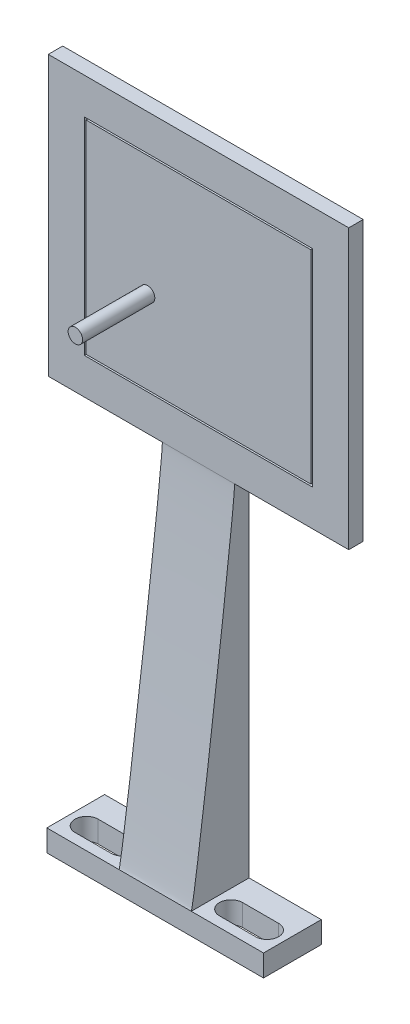
SolidWorks part; units mm, degrees
ref_plane "Front Plane" through (0, 0, 0) normal (0, 0, 1) x (1, 0, 0)
ref_plane "Top Plane" through (0, 0, 0) normal (0, 1, 0) x (1, 0, 0)
ref_plane "Right Plane" through (0, 0, 0) normal (1, 0, 0) x (0, 0, -1)
sketch "Sketch1" plane through (0, 0, 0) normal (0, 0, 1) x (1, 0, 0)
  line L0 (0, -16.6) -> (8.5, -16.6)
  line L1 (0, 0) -> (31.1, 0)
  line L2 (0, 0) -> (0, -28.1)
  line L3 (0, -28.1) -> (31.1, -28.1)
  line L4 (31.1, 0) -> (31.1, -28.1)
  circle A0 centre (8.5, -16.6) radius 1
  dimension "D5" = 2
  dimension "D1" = 28.1
  dimension "D2" = 31.1
  dimension "D3" = 11.5
  dimension "D4" = 8.5
extrude "Boss-Extrude2" add sketch "Sketch1" along normal blind 1.5 contours A0 L2 L3 L4 L1 | A0 region at (15.5754, -14.0408, 0)
sketch "Sketch3" plane through (0, 0, 1.5) normal (0, 0, 1) x (1, 0, 0)
  line L0 (0, -16.6) -> (8.5, -16.6) construction
  line L1 (0, -16.6) -> (8.5, -16.6)
  line L4 (31.1, 0) -> (0, 0)
  line L5 (0, 0) -> (0, -28.1)
  line L6 (0, -28.1) -> (31.1, -28.1)
  line L7 (31.1, -28.1) -> (31.1, 0)
  line L8 (31.1, 0) -> (0, 0)
  line L9 (0, 0) -> (0, -28.1)
  line L10 (0, -28.1) -> (31.1, -28.1)
  line L11 (31.1, -28.1) -> (31.1, 0)
  line L12 (31.1, 0) -> (0, 0)
  line L13 (31.1, -28.1) -> (31.1, 0)
  line L14 (0, -28.1) -> (31.1, -28.1)
  line L15 (0, 0) -> (0, -28.1)
  line L16 (31.1, 0) -> (0, 0)
  line L17 (31.1, -28.1) -> (31.1, 0)
  line L18 (0, -28.1) -> (31.1, -28.1)
  line L19 (0, 0) -> (0, -28.1)
  circle A1 centre (8.5, -16.6) radius 1
  circle A2 centre (8.5, -16.6) radius 1
  dimension "D1" = 0
  dimension "D2" = 0
  dimension "D3" = 0
extrude "Boss-Extrude3" add sketch "Sketch3" along normal blind 10 contours A2 region at (8.5, -15.6283, 1.5)
sketch "Sketch4" plane through (0, 0, 1.5) normal (0, 0, 1) x (1, 0, 0)
  line L1 (0, 0) -> (31.1, 0)
  line L2 (0, 0) -> (0, -28.1)
  line L3 (0, -28.1) -> (31.1, -28.1)
  line L4 (31.1, 0) -> (31.1, -28.1)
  line L5 (-0.25, 0.25) -> (31.35, 0.25)
  line L6 (-0.25, 0.25) -> (-0.25, -28.35)
  line L7 (-0.25, -28.35) -> (31.35, -28.35)
  line L8 (31.35, 0.25) -> (31.35, -28.35)
  line L9 (-5.25, 5.25) -> (36.35, 5.25)
  line L10 (-5.25, 5.25) -> (-5.25, -33.35)
  line L11 (-5.25, -33.35) -> (36.35, -33.35)
  line L12 (36.35, 5.25) -> (36.35, -33.35)
  dimension "D1" = 0.25
  dimension "D2" = 0.25
  dimension "D3" = 0.25
  dimension "D4" = 0.25
  dimension "D5" = 5
  dimension "D6" = 5
  dimension "D7" = 5
  dimension "D8" = 5
extrude "Boss-Extrude4" add sketch "Sketch4" against normal blind 2 separate body contours L12 L9 L10 L11 L5 L8 L7 L6 region at (15.55, 4.6825, 1.5)
sketch "Sketch6" plane through (0, -33.35, 0) normal (0, -1, 0) x (1, 0, 0)
  line L0 (0, 1.5) -> (31.1, 1.5) construction
  line L1 (10.55, 1.5) -> (20.55, 1.5)
  line L2 (10.55, 1.5) -> (10.55, -0.5)
  line L3 (10.55, -0.5) -> (20.55, -0.5)
  line L4 (20.55, 1.5) -> (20.55, -0.5)
  line L5 (-5.25, -0.5) -> (36.35, -0.5) construction
  line L6 (10.55, 1.5) -> (-5.25, 1.5) construction
  line L7 (20.55, 1.5) -> (36.35, 1.5) construction
  dimension "D1" = 10
extrude "Boss-Extrude5" add sketch "Sketch6" along normal blind 48.25
sketch "Sketch7" plane through (0, -81.6, 0) normal (0, -1, 0) x (1, 0, 0)
  line L0 (10.55, 1.5) -> (20.55, 1.5)
  line L1 (10.55, -0.5) -> (20.55, -0.5)
  line L5 (-5.25, 1.5) -> (10.55, 1.5) construction
  line L9 (0.55, 7.5) -> (0.55, 1.5)
  line L11 (30.55, 7.5) -> (30.55, 1.5)
  line L12 (20.55, 1.5) -> (36.35, 1.5) construction
  line L13 (30.55, 1.5) -> (20.55, 1.5)
  line L16 (0.55, 1.5) -> (10.55, 1.5)
  line L17 (0.55, 1.5) -> (0.55, -0.5)
  line L18 (0.55, -0.5) -> (10.55, -0.5)
  line L19 (10.55, 1.5) -> (10.55, -0.5)
  line L20 (30.55, 1.5) -> (20.55, 1.5)
  line L21 (30.55, 1.5) -> (30.55, -0.5)
  line L22 (30.55, -0.5) -> (20.55, -0.5)
  line L23 (20.55, 1.5) -> (20.55, -0.5)
  line L25 (0.55, 7.5) -> (0.55, 1.5)
  line L26 (0.55, 1.5) -> (30.55, 1.5)
  line L27 (30.55, 7.5) -> (30.55, 1.5)
  line L31 (10.55, 1.5) -> (10.55, 7.5)
  line L32 (20.55, 1.5) -> (20.55, 7.5)
  line L33 (0.55, 4.5) -> (30.55, 4.5) construction
  line L36 (3.05, 6.1) -> (8.05, 6.1)
  line L37 (8.05, 2.9) -> (3.05, 2.9)
  line L40 (23.05, 6.1) -> (28.05, 6.1)
  line L41 (28.05, 2.9) -> (23.05, 2.9)
  line L42 (10.55, 7.5) -> (10.55, 1.5)
  line L43 (0.55, 7.5) -> (10.55, 7.5)
  line L44 (20.55, 1.5) -> (20.55, 7.5)
  line L45 (20.55, 1.5) -> (10.55, 1.5)
  line L46 (10.55, 7.5) -> (20.55, 7.5)
  line L47 (20.55, 7.5) -> (30.55, 7.5)
  arc A11 (23.05, 6.1) -> (23.05, 2.9) centre (23.05, 4.5) ccw
  arc A12 (28.05, 6.1) -> (28.05, 2.9) centre (28.05, 4.5) cw
  arc A15 (3.05, 6.1) -> (3.05, 2.9) centre (3.05, 4.5) ccw
  arc A16 (8.05, 6.1) -> (8.05, 2.9) centre (8.05, 4.5) cw
  line M6 (10.55, 1.5) -> (10.55, -0.5)
  line M7 (10.55, -0.5) -> (20.55, -0.5)
  line M8 (20.55, -0.5) -> (20.55, 1.5)
  line M9 (20.55, 1.5) -> (10.55, 1.5)
  dimension "D5" = 1.6
  dimension "D6" = 5
  dimension "D11" = 2.5
  dimension "D9" = 3.2
  dimension "D12" = 0
  dimension "D3" = 1.6
  dimension "D10" = 3.2
  dimension "D1" = 10
  dimension "D2" = 10
  dimension "D4" = 6
  dimension "D7" = 2.5
  dimension "D8" = 5
extrude "Boss-Extrude10" add sketch "Sketch7" along normal blind 3 contours L9 L33 A15 L36 A16 L42 L43 | L33 L25 L16 L31 A16 L37 A15 | L42 L33 L44 L46 | L33 L31 L32 M9 | L33 L32 L13 L27 A12 L41 A11 | L44 L33 A11 L40 A12 L11 L47 | L22 L21 L13 M8 | M9 M6 M7 M8 | L17 L18 L16 M6 region at (15.55, -81.6, 3) region at (5.55, -81.6, 0.5) region at (15.55, -81.6, 0.5) region at (5.55, -81.6, 2.5049) region at (25.55, -81.6, 2.5049) region at (25.55, -81.6, 0.5) region at (5.55, -81.6, 6.4951) region at (15.55, -81.6, 6) region at (25.55, -81.6, 6.4951)
fillet "Fillet5" radius 48.25 1 edges at (15.55, -81.6, 1.5) second distance 6 conic rho 0.05 first distance on face at (15.55, -35.7625, 1.5)
